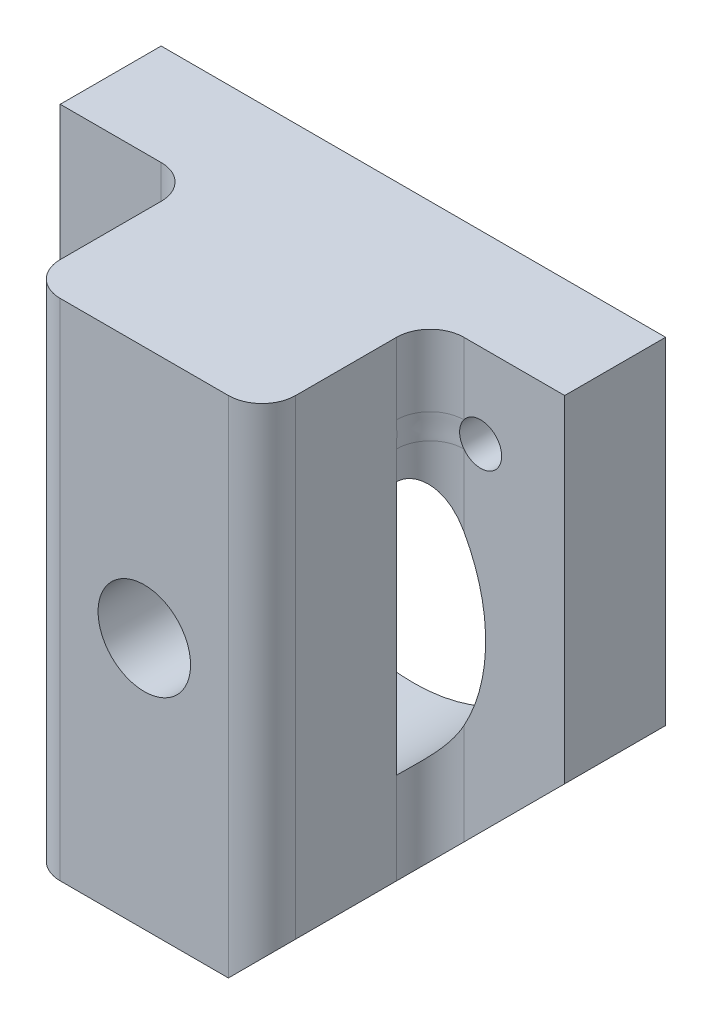
SolidWorks part; units mm, degrees
ref_plane "Front Plane" through (0, 0, 0) normal (0, 0, 1) x (1, 0, 0)
ref_plane "Top Plane" through (0, 0, 0) normal (0, 1, 0) x (1, 0, 0)
ref_plane "Right Plane" through (0, 0, 0) normal (1, 0, 0) x (0, 0, -1)
sketch "Sketch1" plane through (0, 0, 0) normal (0, 0, 1) x (1, 0, 0)
  line L0 (-15, -15) -> (5, -15)
  line L1 (5, -15) -> (15, -5)
  line L2 (-15, -15) -> (-15, 15)
  line L3 (-15, 15) -> (15, 15)
  line L4 (15, -5) -> (15, 15)
  line L5 (-15, -15) -> (15, 15) construction
  line L6 (-15, 15) -> (15, -15) construction
  circle A0 centre (-10, 10) radius 1.25
  circle A1 centre (10, 10) radius 1.25
  circle A2 centre (-10, -10) radius 1.25
  point P0 (0, 0)
  point P11 (0, 0)
  point P12 (15.8914, -4.0196)
  point P14 (0, 0)
  point P16 (0, 0)
  dimension "D3" = 2.5
  dimension "D6" = 20
  dimension "D1" = 30
  dimension "D2" = 30
  dimension "D4" = 20
  dimension "D5" = 135
extrude "Main" add sketch "Sketch1" along normal blind 16
sketch "Sketch2" plane through (0, 0, 0) normal (0, 0, 1) x (1, 0, 0)
  line L0 (-15, -15) -> (15, 15) construction
  line L1 (-15, 15) -> (15, -15) construction
  line L2 (15, -5) -> (15, 15) construction
  line L3 (15, 15) -> (-15, 15) construction
  circle A0 centre (0, 0) radius 10.3
  point P2 (15, -15)
  point P6 (-15, -15)
  point P12 (0, 0)
  point P15 (15, 15)
  point P18 (0, 0)
  point P19 (-15, -15)
  point P20 (15, 15)
  dimension "D1" = 20.6
extrude "CentralHole" cut sketch "Sketch2" along normal blind 8
sketch "Sketch5" plane through (0, 0, 16) normal (0, 0, 1) x (1, 0, 0)
  line L0 (15, 15) -> (-15, 15) construction
  line L1 (15, -15) -> (7, -15)
  line L2 (15, -15) -> (15, 15)
  line L3 (15, 15) -> (7, 15)
  line L4 (7, -15) -> (7, 15)
  line L5 (-15, -15) -> (5, -15) construction
  line L6 (-15, -15) -> (-7, -15)
  line L7 (-15, -15) -> (-15, 15)
  line L8 (-15, 15) -> (-7, 15)
  line L9 (-7, -15) -> (-7, 15)
  line L10 (15, -5) -> (15, 15) construction
  circle A0 centre (0, 0) radius 2.75
  point P17 (-15, -15)
  point P19 (13.0538, -15)
  point P20 (15, 15)
  dimension "D3" = 5.5
  dimension "D1" = 8
  dimension "D2" = 8
extrude "Cut-Extrude3" cut sketch "Sketch5" against normal blind 10
fillet "Fillet1" radius 2 6 edges at (-7, 0, 16) (7, 1, 16) (-7, -11.2779, 6) (-7, 11.2779, 6) (7, 11.2779, 6) (7, -10.2779, 6)
